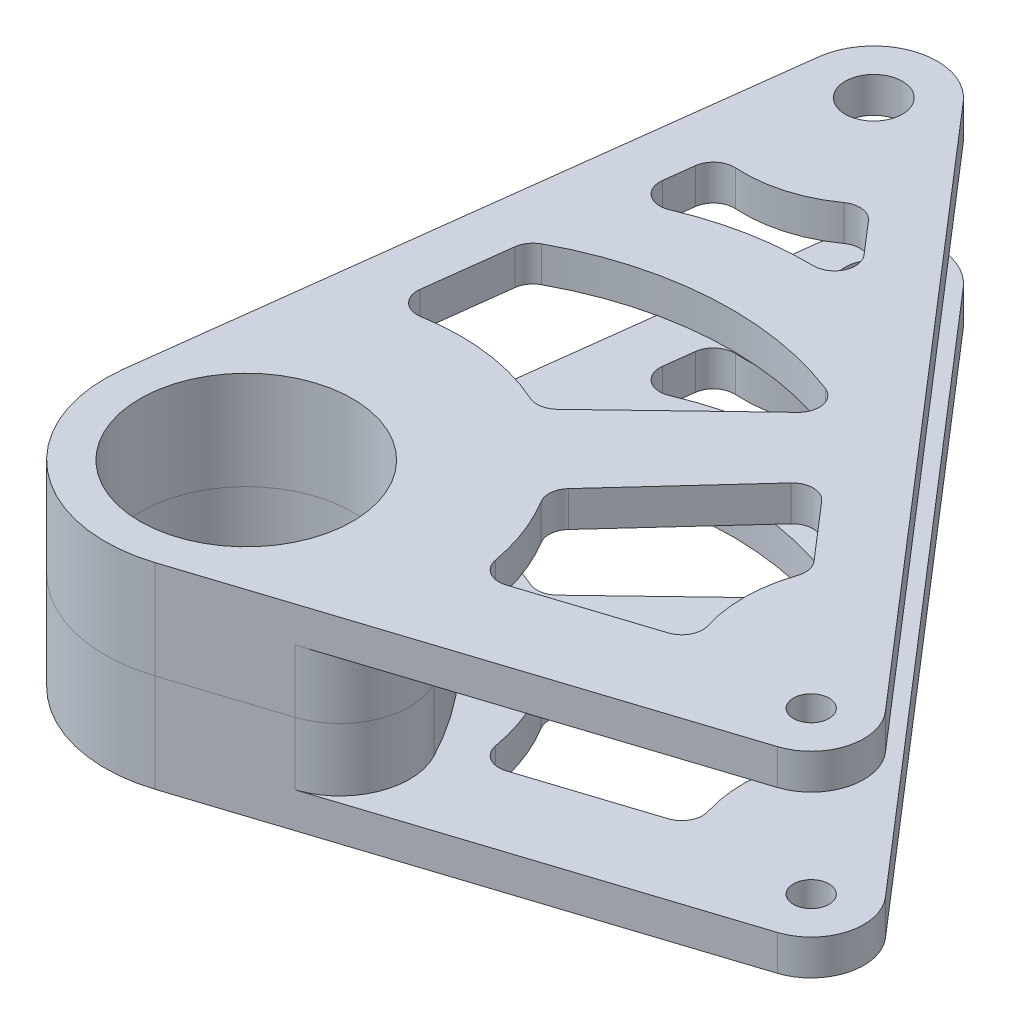
SolidWorks part; units mm, degrees
ref_plane "Front Plane" through (0, 0, 0) normal (0, 0, 1) x (1, 0, 0)
ref_plane "Top Plane" through (0, 0, 0) normal (0, 1, 0) x (1, 0, 0)
ref_plane "Right Plane" through (0, 0, 0) normal (1, 0, 0) x (0, 0, -1)
sketch "Sketch1" plane through (0, 0, 0) normal (0, 1, 0) x (1, 0, 0)
  line L0 (0, 90) -> (0, 0) construction
  line L1 (-9.0299, 91.1274) -> (-20.094, 2.5088)
  line L2 (6.8901, 95.9445) -> (77.0633, 14.6087)
  line L3 (6.2184, -19.2716) -> (73.6652, 2.4916)
  circle A0 centre (0, 0) radius 15.25
  circle A1 centre (0, 90) radius 4.1
  circle A2 centre (71.3468, 9.6768) radius 2.55
  circle A3 centre (0, 90) radius 9.1
  circle A4 centre (0, 0) radius 20.25
  circle A5 centre (71.3468, 9.6768) radius 7.55
  dimension "D1" = 8.2
  dimension "D2" = 30.5
  dimension "D3" = 5.1
  dimension "D5" = 72
  dimension "D4" = 90
  dimension "D7" = 65
  dimension "D6" = 5
extrude "Boss-Extrude1" add sketch "Sketch1" along normal blind 5.08 contours A1 A3 | A3 L0 A4 L3 A5 L2 | A4 A0 | L0 A3 L1 A4 | A5 A2 region at (-6.6287, 0, -84.1474) region at (29.7679, 0, -32.9531) region at (-7.7283, 0, -46.5593) region at (13.9139, 0, -13.9139) region at (78.2234, 0, -12.2332)
sketch "Sketch3" plane through (0, 5.08, 0) normal (0, 1, 0) x (1, 0, 0)
  line L0 (-4.3566, 68.7531) -> (-4.878, 64.5764)
  line L1 (14.885, 74.3483) -> (18.8453, 69.758)
  line L2 (-7.227, 45.7623) -> (-8.7381, 33.6591)
  line L3 (-9.0299, 91.1274) -> (-20.094, 2.5088)
  line L4 (6.2184, -19.2716) -> (73.6652, 2.4916)
  line L5 (77.0633, 14.6087) -> (6.8901, 95.9445)
  line L6 (-9.0299, 91.1274) -> (-20.094, 2.5088)
  line L7 (6.2184, -19.2716) -> (73.6652, 2.4916)
  line L8 (77.0633, 14.6087) -> (6.8901, 95.9445)
  line L9 (33.6182, 45.4602) -> (16.0066, 28.6079)
  line L10 (51.7364, 8.7886) -> (34.1708, 3.1207)
  line L11 (53.2942, 28.131) -> (46.3765, 36.1492)
  line L12 (41.8914, 36.2143) -> (26.6598, 19.5625)
  circle A0 centre (0, 90) radius 9.1
  circle A1 centre (0, 0) radius 20.25
  circle A2 centre (71.3468, 9.6768) radius 7.55
  arc A3 (-1.1886, 71.3754) -> (10.8667, 74.8276) centre (0, 90) ccw
  arc A4 (30.2969, 5.4451) -> (26.3093, 15.9803) centre (0, 0) ccw
  arc A6 (-20.094, 2.5088) -> (6.2184, -19.2716) centre (0, 0) ccw
  arc A7 (73.6652, 2.4916) -> (77.0633, 14.6087) centre (71.3468, 9.6768) ccw
  arc A8 (6.8901, 95.9445) -> (-9.0299, 91.1274) centre (0, 90) ccw
  arc A9 (-20.094, 2.5088) -> (6.2184, -19.2716) centre (0, 0) ccw
  arc A10 (73.6652, 2.4916) -> (77.0633, 14.6087) centre (71.3468, 9.6768) ccw
  arc A11 (6.8901, 95.9445) -> (-9.0299, 91.1274) centre (0, 90) ccw
  arc A12 (-0.7285, 61.4435) -> (16.5217, 64.7988) centre (15.7875, 22.5525) cw
  arc A13 (-5.6779, 48.029) -> (32.6322, 50.4235) centre (16.063, 7.8532) cw
  arc A14 (53.6802, 12.5333) -> (53.8612, 25.2001) centre (73.1823, 18.5893) cw
  arc A15 (12.6952, 28.0425) -> (-5.2496, 30.3313) centre (0, 0) ccw
  arc A16 (53.2942, 28.131) -> (53.8612, 25.2001) centre (51.0228, 26.1713) cw
  arc A17 (51.7364, 8.7886) -> (53.6802, 12.5333) centre (50.8151, 11.6437) ccw
  arc A18 (34.1708, 3.1207) -> (30.2969, 5.4451) centre (33.2495, 5.9757) cw
  arc A19 (26.6598, 19.5625) -> (26.3093, 15.9803) centre (28.8734, 17.5377) ccw
  arc A20 (46.3765, 36.1492) -> (41.8914, 36.2143) centre (44.105, 34.1894) ccw
  arc A21 (32.6322, 50.4235) -> (33.6182, 45.4602) centre (31.5441, 47.6278) cw
  arc A22 (16.0066, 28.6079) -> (12.6952, 28.0425) centre (13.9325, 30.7754) cw
  arc A23 (-8.7381, 33.6591) -> (-5.2496, 30.3313) centre (-5.7612, 33.2874) ccw
  arc A24 (-7.227, 45.7623) -> (-5.6779, 48.029) centre (-4.2501, 45.3906) cw
  arc A25 (18.8453, 69.758) -> (16.5217, 64.7988) centre (16.5739, 67.7983) cw
  arc A26 (14.885, 74.3483) -> (10.8667, 74.8276) centre (12.6136, 72.3886) ccw
  arc A27 (-4.878, 64.5764) -> (-0.7285, 61.4435) centre (-1.9011, 64.2048) ccw
  arc A28 (-4.3566, 68.7531) -> (-1.1886, 71.3754) centre (-1.3797, 68.3815) cw
  point P33 (36.8351, 48.5384)
  point P49 (14.4912, 27.1579)
  dimension "D1" = 0
  dimension "D2" = 3
extrude "Cut-Extrude1" cut sketch "Sketch3" against normal through all contours L0 A12 L1 A3 | L10 A14 A13 L2 A4 | A24 L2 A23 A15 A22 L9 A21 A13 region at (6.9747, 5.08, -68.0651) region at (11.1766, 5.08, -41.7744) region at (41.0253, 5.08, -18.8935)
sketch "Sketch2" plane through (0, 5.08, 0) normal (0, 1, 0) x (1, 0, 0)
  line L0 (6.2184, -19.2716) -> (73.6652, 2.4916) construction
  line L1 (-9.0299, 91.1274) -> (-20.094, 2.5088) construction
  line L2 (6.2184, -19.2716) -> (21.3577, -14.3866)
  line L3 (-18.0866, 18.5868) -> (-20.094, 2.5088)
  arc A0 (-20.094, 2.5088) -> (6.2184, -19.2716) centre (0, 0) ccw construction
  circle A1 centre (0, 0) radius 15.25 construction
  arc A2 (-20.094, 2.5088) -> (6.2184, -19.2716) centre (0, 0) ccw
  circle A3 centre (0, 0) radius 15.25
  arc A4 (-5.1389, 26.8795) -> (27.1531, -0.2448) centre (-21.8602, -25.8117) cw
  arc A5 (27.1531, -0.2448) -> (21.3577, -14.3866) centre (18.2869, -4.8697) cw
  arc A6 (-5.1389, 26.8795) -> (-18.0866, 18.5868) centre (-8.1637, 17.348) ccw
  point P15 (31.4366, -11.1344)
  point P18 (-16.7574, 29.2331)
  dimension "D1" = 10
extrude "Boss-Extrude2" add sketch "Sketch2" along normal blind 9
mirror "Mirror1" about plane through (0, 14.08, 0) normal (0, 1, 0) of bodies 102
ref_plane "Plane1" through (0, 14.08, 0) normal (0, -1, 0) x (-1, 0, 0)
ref_axis "Axis1" through (71.3468, 5.08, -9.6768) along (0, -1, 0)
ref_point "Pushrod Pt"
